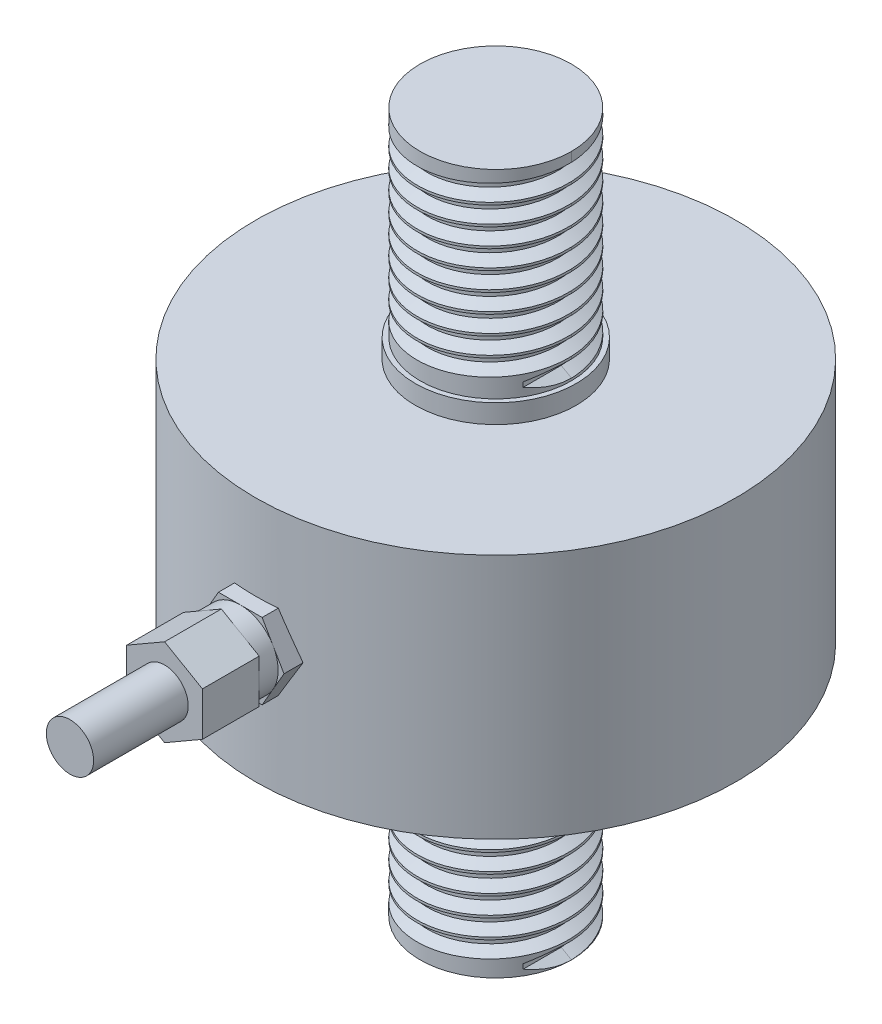
SolidWorks part; units mm, degrees
material "Plain Carbon Steel"
ref_plane "Front Plane" through (0, 0, 0) normal (0, 0, 1) x (1, 0, 0)
ref_plane "Top Plane" through (0, 0, 0) normal (0, 1, 0) x (1, 0, 0)
ref_plane "Right Plane" through (0, 0, 0) normal (1, 0, 0) x (0, 0, -1)
sketch "Sketch1" plane through (0, 0, 0) normal (0, 1, 0) x (1, 0, 0)
  circle A0 centre (0, 0) radius 12.7
  dimension "D1" = 25.4
extrude "Boss-Extrude1" add sketch "Sketch1" along normal blind 13
sketch "Sketch2" plane through (0, 13, 0) normal (0, 1, 0) x (1, 0, 0)
  circle A0 centre (0, 0) radius 4.25
  dimension "D1" = 8.5
extrude "Boss-Extrude2" add sketch "Sketch2" along normal blind 1
sketch "Sketch3" plane through (0, 14, 0) normal (0, 1, 0) x (1, 0, 0)
  circle A0 centre (0, 0) radius 4
  dimension "D1" = 8
extrude "Boss-Extrude3" add sketch "Sketch3" along normal blind 10.5
sketch "Sketch4" plane through (0, 0, 0) normal (0, -1, 0) x (1, 0, 0)
  circle A0 centre (0, 0) radius 5
  dimension "D1" = 10
extrude "Boss-Extrude4" add sketch "Sketch4" along normal blind 2
sketch "Sketch5" plane through (0, -2, 0) normal (0, -1, 0) x (1, 0, 0)
  circle A0 centre (0, 0) radius 4
  dimension "D1" = 8
extrude "Boss-Extrude5" add sketch "Sketch5" along normal blind 10.5
thread "Thread1" pitch 1 method cut profile "Thread Profile1" start angle 0, offset 0, length 9.5, pitch 1, diameter 8
ref_plane "Plane1" through (-4, 24.5, 0) normal (0, 0, 1) x (-1, 0, 0)
sketch "Thread Profile1" plane through (-4, 24.5, 0) normal (0, 0, 1) x (-1, 0, 0)
  line L0 (0, 0) -> (0, 1) construction
  line L11 (0, 0) -> (0, 0.875)
  line L12 (0, 0.875) -> (-0.5413, 0.5625)
  line L13 (-0.5413, 0.5625) -> (-0.5413, 0.3125)
  line L15 (-0.5413, 0.3125) -> (0, 0)
  line L17 (-0.5413, 0.4375) -> (0, 0.4375) construction
  point P2 (0, 0)
  dimension "Pitch" = 1
  dimension "Profile_Angle" = 60
  dimension "Profile_Land" = 0.25
  dimension "Profile_Height" = 0.5413
sketch "Sketch11" plane through (0, 0, 0) normal (0, 0, -1) x (-1, 0, 0)
  line L4 (4, 24.5) -> (3.4587, 24.1875)
  line L5 (3.4587, 24.1875) -> (3.4587, 23.9375)
  line L6 (3.4587, 23.9375) -> (4, 23.625)
  line L7 (4, 23.625) -> (4, 24.5)
  line L8 (4, 24.5) -> (3.4587, 24.1875)
  line L9 (3.4587, 24.1875) -> (3.4587, 23.9375)
  line L10 (3.4587, 23.9375) -> (4, 23.625)
  line L11 (4, 23.625) -> (4, 24.5)
  dimension "D1" = 0
extrude "Cut-Extrude1" cut sketch "Sketch11" against normal through all
thread "Thread2" pitch 1 method cut profile "Thread Profile2" start angle 0, offset 0, length 9.5, pitch 1, diameter 8
ref_plane "Plane2" through (4, -12.5, 0) normal (0, 0, 1) x (1, 0, 0)
sketch "Thread Profile2" plane through (4, -12.5, 0) normal (0, 0, 1) x (1, 0, 0)
  line L0 (0, 0) -> (0, 1) construction
  line L11 (0, 0) -> (0, 0.875)
  line L12 (0, 0.875) -> (-0.5413, 0.5625)
  line L13 (-0.5413, 0.5625) -> (-0.5413, 0.3125)
  line L15 (-0.5413, 0.3125) -> (0, 0)
  line L17 (-0.5413, 0.4375) -> (0, 0.4375) construction
  point P2 (0, 0)
  dimension "Pitch" = 1
  dimension "Profile_Angle" = 60
  dimension "Profile_Land" = 0.25
  dimension "Profile_Height" = 0.5413
sketch "Sketch14" plane through (0, 0, 0) normal (0, 0, -1) x (-1, 0, 0)
  line L4 (-4, -12.5) -> (-3.4587, -12.1875)
  line L5 (-3.4587, -12.1875) -> (-3.4587, -11.9375)
  line L6 (-3.4587, -11.9375) -> (-4, -11.625)
  line L7 (-4, -11.625) -> (-4, -12.5)
  line L8 (-4, -12.5) -> (-3.4587, -12.1875)
  line L9 (-3.4587, -12.1875) -> (-3.4587, -11.9375)
  line L10 (-3.4587, -11.9375) -> (-4, -11.625)
  line L11 (-4, -11.625) -> (-4, -12.5)
  dimension "D1" = 0
extrude "Cut-Extrude2" cut sketch "Sketch14" against normal through all
sketch "Sketch15" plane through (0, 0, 0) normal (0, 0, -1) x (-1, 0, 0)
  line L4 (-3.4587, 14.6875) -> (-4, 15)
  line L5 (-4, 15) -> (-4, 14.125)
  line L6 (-4, 14.125) -> (-3.4587, 14.4375)
  line L7 (-3.4587, 14.4375) -> (-3.4587, 14.6875)
  line L8 (-3.4587, 14.6875) -> (-4, 15)
  line L9 (-4, 15) -> (-4, 14.125)
  line L10 (-4, 14.125) -> (-3.4587, 14.4375)
  line L11 (-3.4587, 14.4375) -> (-3.4587, 14.6875)
  dimension "D1" = 0
extrude "Cut-Extrude3" cut sketch "Sketch15" against normal through all
sketch "Sketch16" plane through (0, 0, 0) normal (0, 0, -1) x (-1, 0, 0)
  line L4 (3.4587, -2.6875) -> (4, -3)
  line L5 (4, -3) -> (4, -2.125)
  line L6 (4, -2.125) -> (3.4587, -2.4375)
  line L7 (3.4587, -2.4375) -> (3.4587, -2.6875)
  line L8 (3.4587, -2.6875) -> (4, -3)
  line L9 (4, -3) -> (4, -2.125)
  line L10 (4, -2.125) -> (3.4587, -2.4375)
  line L11 (3.4587, -2.4375) -> (3.4587, -2.6875)
  dimension "D1" = 0
extrude "Cut-Extrude4" cut sketch "Sketch16" against normal through all
ref_plane "Plane3" through (0, 0, 12.5) normal (0, 0, 1) x (1, 0, 0)
sketch "Sketch17" plane through (0, 0, 12.5) normal (0, 0, 1) x (1, 0, 0)
  line L1 (1.1547, 4.5) -> (2.3094, 6.5)
  line L2 (2.3094, 6.5) -> (1.1547, 8.5)
  line L3 (1.1547, 8.5) -> (-1.1547, 8.5)
  line L4 (-1.1547, 8.5) -> (-2.3094, 6.5)
  line L5 (-2.3094, 6.5) -> (-1.1547, 4.5)
  line L6 (-1.1547, 4.5) -> (1.1547, 4.5)
  circle A0 centre (0, 6.5) radius 2 construction
  dimension "D1" = 4
extrude "Boss-Extrude6" add sketch "Sketch17" along normal blind 1
sketch "Sketch18" plane through (0, 0, 13.5) normal (0, 0, 1) x (1, 0, 0)
  circle A0 centre (0, 6.5) radius 2
  dimension "D1" = 4
extrude "Boss-Extrude7" add sketch "Sketch18" along normal blind 1
sketch "Sketch19" plane through (0, 0, 14.5) normal (0, 0, 1) x (1, 0, 0)
  line L1 (0, 4.1906) -> (2, 5.3453)
  line L2 (2, 5.3453) -> (2, 7.6547)
  line L3 (2, 7.6547) -> (0, 8.8094)
  line L4 (0, 8.8094) -> (-2, 7.6547)
  line L5 (-2, 7.6547) -> (-2, 5.3453)
  line L6 (-2, 5.3453) -> (0, 4.1906)
  circle A0 centre (0, 6.5) radius 2 construction
  dimension "D1" = 4
extrude "Boss-Extrude8" add sketch "Sketch19" along normal blind 3
sketch "Sketch20" plane through (0, 0, 17.5) normal (0, 0, 1) x (1, 0, 0)
  circle A0 centre (0, 6.5) radius 1.25
  dimension "D1" = 2.5
extrude "Boss-Extrude9" add sketch "Sketch20" along normal blind 5 separate body
